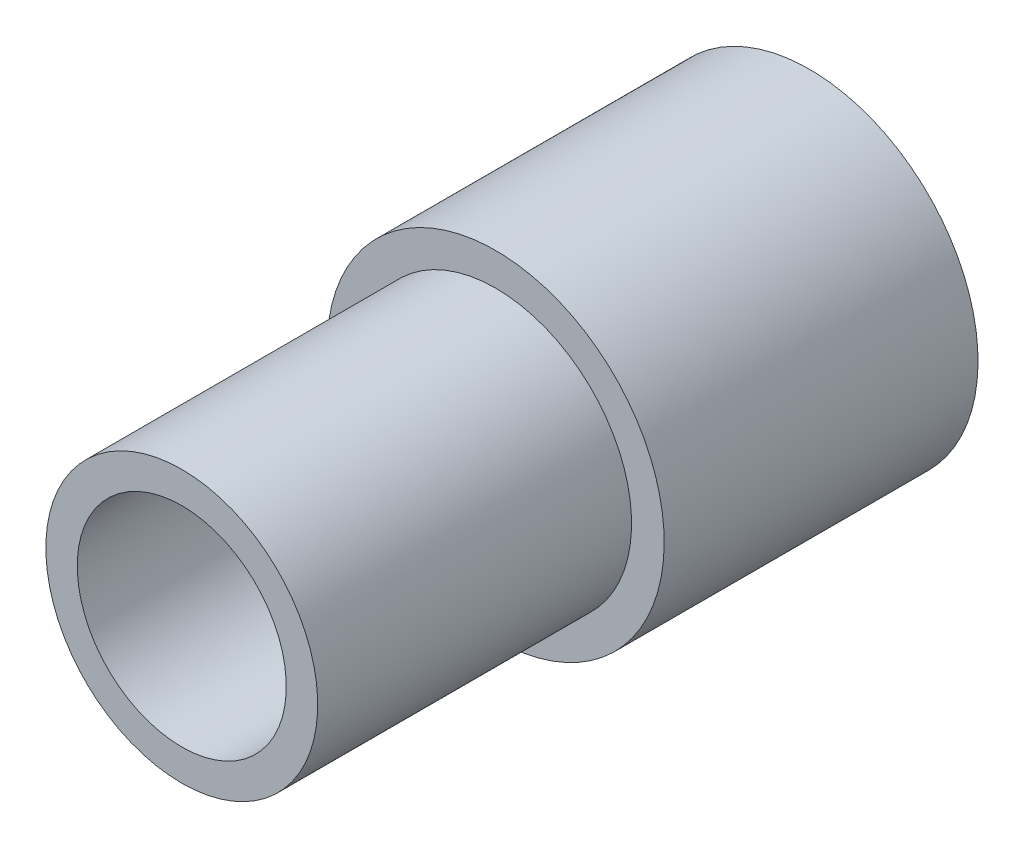
SolidWorks part; units mm, degrees
material "PET"
ref_plane "Front" through (0, 0, 0) normal (0, 0, 1) x (1, 0, 0)
ref_plane "Top" through (0, 0, 0) normal (0, 1, 0) x (1, 0, 0)
ref_plane "Right" through (0, 0, 0) normal (1, 0, 0) x (0, 0, -1)
ref_axis "Axis1" through (0, 0, 55) along (0, 0, -1)
sketch "Sketch1" plane through (0, 0, 0) normal (1, 0, 0) x (0, 0, -1)
  line L0 (-27.655, 0) -> (27.655, 0) construction
  line L1 (-27.655, 11) -> (-2.255, 11)
  line L2 (-2.255, 11) -> (-2.255, 13.64)
  line L3 (-2.255, 13.64) -> (23.145, 13.64)
  line L4 (-27.655, 8.46) -> (0.285, 8.46)
  line L5 (0.285, 8.46) -> (0.285, 11.1)
  line L6 (0.285, 11.1) -> (23.145, 11.1)
  line L7 (-27.655, 11) -> (-27.655, 8.46)
  line L8 (23.145, 13.64) -> (23.145, 11.1)
  line L9 (-1.2986, 0) -> (20.1081, 0)
  arc A0 (20.1081, 0) -> (-1.2986, 0) centre (9.4048, 0) ccw
  point P4 (0, 0)
  dimension "D5" = 10.7033
  dimension "D1" = 11
  dimension "D2" = 2.54
  dimension "D3" = 11.1
  dimension "D4" = 50.8
  dimension "D6" = 0.285
  dimension "D7" = 9.4048
revolve "Revolve1" add sketch "Sketch1" angle 360 about L0
